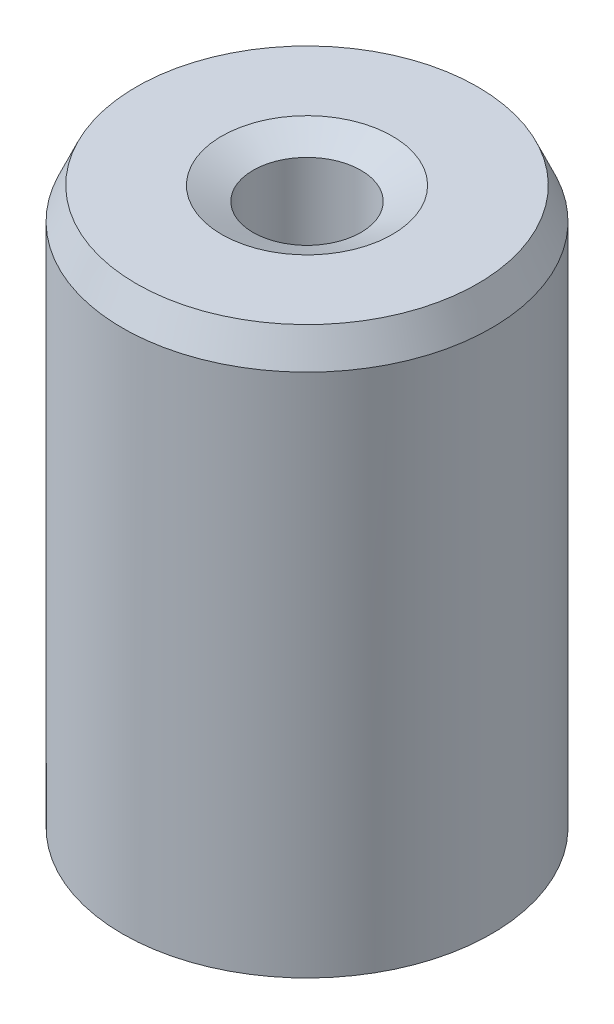
SolidWorks part; units mm, degrees
ref_plane "Front Plane" through (0, 0, 0) normal (0, 0, 1) x (1, 0, 0)
ref_plane "Top Plane" through (0, 0, 0) normal (0, 1, 0) x (1, 0, 0)
ref_plane "Right Plane" through (0, 0, 0) normal (1, 0, 0) x (0, 0, -1)
sketch "Sketch1" plane through (0, 0, 0) normal (0, 1, 0) x (1, 0, 0)
  circle A0 centre (0, 0) radius 5
  dimension "SLEEVE_OD" = 10
extrude "Boss-Extrude1" add sketch "Sketch1" along normal blind 15.442
sketch "Sketch2" plane through (0, 0, 0) normal (0, 1, 0) x (1, 0, 0)
  circle A0 centre (0, 0) radius 1.4605
  dimension "BORE_D" = 2.9211
extrude "Cut-Extrude1" cut sketch "Sketch2" along normal through all
chamfer "Chamfer1" distance 0.85 angle 23.947 4 edges at (0, 15.442, 1.4605) (0, 0, 1.4605) (0, 0, 5) (0, 15.442, 5) first distance on face at (0, 15.442, 1.4605) first distance on face at (0, 0, 1.4605) first distance on face at (0, 15.442, 5)
